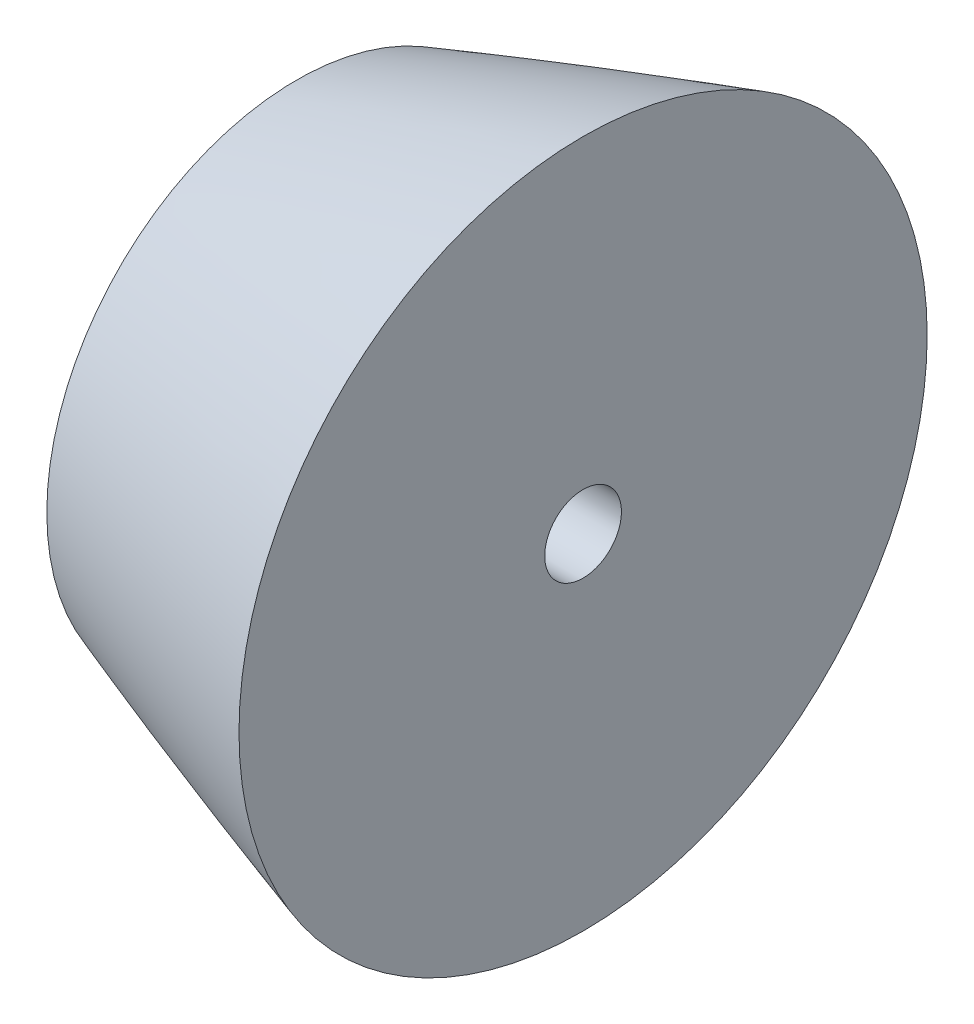
SolidWorks part; units mm, degrees
material "6061-T6 (SS)"
ref_plane "Front Plane" through (0, 0, 0) normal (0, 0, 1) x (1, 0, 0)
ref_plane "Top Plane" through (0, 0, 0) normal (0, 1, 0) x (1, 0, 0)
ref_plane "Right Plane" through (0, 0, 0) normal (1, 0, 0) x (0, 0, -1)
sketch "Sketch1" plane through (0, 0, 0) normal (0, 0, 1) x (1, 0, 0)
  line L0 (0, 0) -> (457.2, 0)
  line L2 (457.2, 88.9) -> (457.2, 0) construction
  line L5 (457.2, 0) -> (469.893, 0)
  line L7 (457.2, 88.9) -> (469.893, 88.9)
  line L8 (469.893, 0) -> (469.893, 88.9)
  line L15 (457.2, 0) -> (-3.2335, 0) construction
  line L20 (-3.2335, 0) -> (0, 0) construction
  spline S0 degree 4 poles (0, 0) (0.0023, 0.0117) (0.0082, 0.0346) (0.0259, 0.0787) (0.0695, 0.163) (0.1339, 0.2631) (0.2191, 0.3779) (0.337, 0.5207) (0.5083, 0.7099) (0.7967, 0.9963) (1.2974, 1.437) (2.1714, 2.1155) (3.7007, 3.1561) (6.4159, 4.7683) (11.1362, 7.1982) (18.8825, 10.6592) (32.1618, 15.8286) (51.2292, 22.2419) (75.2304, 29.3379) (102.9883, 36.6578) (131.6198, 43.512) (160.3745, 49.8273) (189.2277, 55.6742) (218.164, 61.0945) (247.1725, 66.1133) (276.2458, 70.7417) (305.3786, 74.9797) (334.5673, 78.8147) (363.8094, 82.22) (389.4419, 84.7797) (411.4452, 86.618) (428.6335, 87.7745) (439.7385, 88.3707) (448.4263, 88.7187) (453.4393, 88.8519) (455.9463, 88.8945) (457.2, 88.9) knots 0 0 0 0 0 0.000101 0.000202 0.000405 0.000809 0.001116 0.001422 0.001985 0.002988 0.004584 0.007113 0.011426 0.01877 0.031526 0.052412 0.083828 0.140383 0.203215 0.266046 0.328877 0.391708 0.454539 0.51737 0.580202 0.643033 0.705864 0.768695 0.831526 0.894357 0.925773 0.957189 0.978594 0.989297 1 1 1 1 1 construction
  spline S1 degree 4 poles (0, 0) (0.0023, 0.0117) (0.0082, 0.0346) (0.0259, 0.0787) (0.0695, 0.163) (0.1339, 0.2631) (0.2191, 0.3779) (0.337, 0.5207) (0.5083, 0.7099) (0.7967, 0.9963) (1.2974, 1.437) (2.1714, 2.1155) (3.7007, 3.1561) (6.4159, 4.7683) (11.1362, 7.1982) (18.8825, 10.6592) (32.1618, 15.8286) (51.2292, 22.2419) (75.2304, 29.3379) (102.9883, 36.6578) (131.6198, 43.512) (160.3745, 49.8273) (189.2277, 55.6742) (218.164, 61.0945) (247.1725, 66.1133) (276.2458, 70.7417) (305.3786, 74.9797) (334.5673, 78.8147) (363.8094, 82.22) (389.4419, 84.7797) (411.4452, 86.618) (428.6335, 87.7745) (439.7385, 88.3707) (448.4263, 88.7187) (453.4393, 88.8519) (455.9463, 88.8945) (457.2, 88.9) knots 0 0 0 0 0 0.000101 0.000202 0.000405 0.000809 0.001116 0.001422 0.001985 0.002988 0.004584 0.007113 0.011426 0.01877 0.031526 0.052412 0.083828 0.140383 0.203215 0.266046 0.328877 0.391708 0.454539 0.51737 0.580202 0.643033 0.705864 0.768695 0.831526 0.894357 0.925773 0.957189 0.978594 0.989297 1 1 1 1 1
  dimension "D1" = 457.2
revolve "Revolve3" add sketch "Sketch1" angle 360 about L0
ref_plane "Plane1" through (-3.2335, 0, 0) normal (1, 0, 0) x (0, 0, -1)
ref_plane "Plane2" through (34.8665, 0, 0) normal (1, 0, 0) x (0, 0, -1)
sketch "Sketch2" plane through (34.8665, 0, 0) normal (1, 0, 0) x (0, 0, -1)
  circle A2 centre (0, 0) radius 88.9 construction
  circle A3 centre (0, 0) radius 88.9
ref_plane "Plane3" through (53.9165, 0, 0) normal (1, 0, 0) x (0, 0, -1)
sketch "Sketch4" plane through (53.9165, 0, 0) normal (1, 0, 0) x (0, 0, -1)
  circle A0 centre (0, 0) radius 88.9 construction
  circle A1 centre (0, 0) radius 88.9
extrude "Cut-Extrude2" cut sketch "Sketch4" along normal through all
extrude "Cut-Extrude3" cut sketch "Sketch2" against normal through all contours A3
hole_wizard "1/4-20 Tapped Hole1" positions "Sketch5" profile "Sketch6" tap size "1/4-20" standard "ANSI Inch" end condition through all
sketch "Sketch5" plane through (53.9165, 0, 0) normal (1, 0, 0) x (0, 0, -1)
  point P0 (0, 0)
sketch "Sketch6" plane through (53.9165, 0, 0) normal (0, 1, 0) x (0, 0, -1)
  line L0 (0, 0) -> (0, 19.05)
  line L1 (0, 19.05) -> (2.5527, 19.05)
  line L2 (2.5527, 19.05) -> (2.5527, 0)
  line L5 (2.5527, 0) -> (0, 0)
  line L11 (0, -6.35) -> (0, 107.95) construction
  dimension "Thru Tap Drill Dia." = 5.1054
  dimension "Thru Tap Drill Depth" = 19.05
cosmetic thread "Hole Thread1" parameters "D2"=6.35
